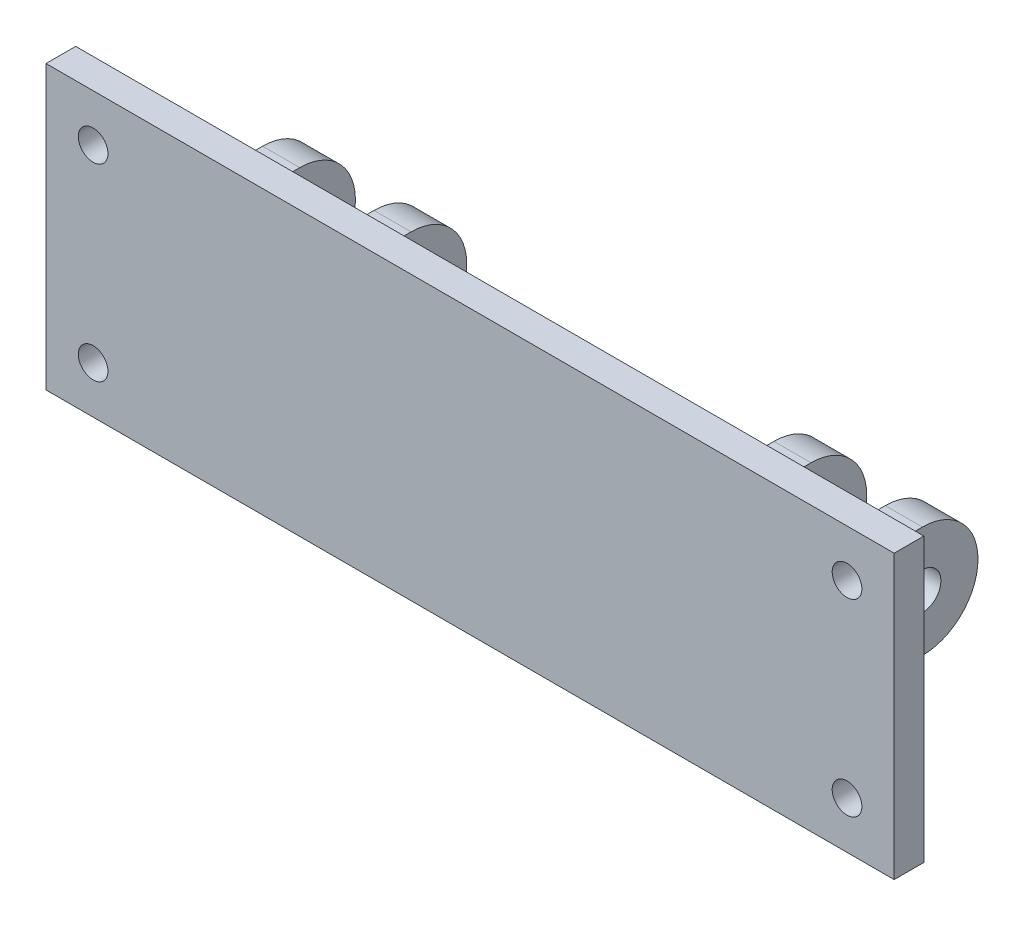
SolidWorks part; units mm, degrees
ref_plane "Front Plane" through (0, 0, 0) normal (0, 0, 1) x (1, 0, 0)
ref_plane "Top Plane" through (0, 0, 0) normal (0, 1, 0) x (1, 0, 0)
ref_plane "Right Plane" through (0, 0, 0) normal (1, 0, 0) x (0, 0, -1)
sketch "Sketch1" plane through (0, 0, 0) normal (0, 0, 1) x (1, 0, 0)
  line L0 (-101.6, 25.4) -> (-101.6, 38.1) construction
  line L1 (-114.3, 38.1) -> (114.3, 38.1)
  line L2 (-114.3, 38.1) -> (-114.3, -38.1)
  line L3 (-114.3, -38.1) -> (114.3, -38.1)
  line L4 (114.3, 38.1) -> (114.3, -38.1)
  line L5 (-58.9, 15) -> (-48.9, 15)
  line L6 (-88.9, 15) -> (-78.9, 15)
  line L7 (-101.6, 25.4) -> (-114.3, 25.4) construction
  line L8 (-88.9, 15) -> (-88.9, -15)
  line L9 (-88.9, -15) -> (-78.9, -15)
  line L10 (-78.9, 15) -> (-78.9, -15)
  line L11 (-88.9, 15) -> (-78.9, -15) construction
  line L12 (-88.9, -15) -> (-78.9, 15) construction
  line L13 (-58.9, 15) -> (-58.9, -15)
  line L14 (-58.9, -15) -> (-48.9, -15)
  line L15 (-48.9, 15) -> (-48.9, -15)
  line L16 (-58.9, 15) -> (-48.9, -15) construction
  line L17 (-58.9, -15) -> (-48.9, 15) construction
  line L18 (0, 0) -> (0, -38.1) construction
  line L19 (58.9, -15) -> (48.9, 15) construction
  line L20 (58.9, 15) -> (48.9, -15) construction
  line L21 (88.9, -15) -> (78.9, 15) construction
  line L22 (88.9, 15) -> (78.9, -15) construction
  line L23 (48.9, 15) -> (48.9, -15)
  line L24 (58.9, -15) -> (48.9, -15)
  line L25 (58.9, 15) -> (58.9, -15)
  line L26 (78.9, 15) -> (78.9, -15)
  line L27 (88.9, -15) -> (78.9, -15)
  line L28 (88.9, 15) -> (88.9, -15)
  line L29 (88.9, 15) -> (78.9, 15)
  line L30 (58.9, 15) -> (48.9, 15)
  circle A0 centre (-101.6, 25.4) radius 4
  circle A7 centre (101.6, 25.4) radius 4
  circle A8 centre (101.6, -25.4) radius 4
  circle A9 centre (-101.6, -25.4) radius 4
  point P0 (0, 0)
  point P16 (-83.9, 0)
  point P23 (-53.9, 0)
  point P36 (53.9, 0)
  point P37 (83.9, 0)
  dimension "D4" = 8
  dimension "D8" = 12.7
  dimension "D6" = 8
  dimension "D7" = 12.7
  dimension "D9" = 8
  dimension "D10" = 12.7
  dimension "D11" = 12.7
  dimension "D12" = 8
  dimension "D13" = 12.7
  dimension "D1" = 76.2
  dimension "D2" = 228.6
  dimension "D3" = 12.7
  dimension "D5" = 12.7
  dimension "D14" = 12.7
  dimension "D15" = 30
  dimension "D16" = 10
  dimension "D17" = 38.1
  dimension "D18" = 25.4
  dimension "D20" = 114.3
  dimension "D21" = 38.1
  dimension "D19" = 2
extrude "Boss-Extrude1" add sketch "Sketch1" along normal blind 8 contours L10 L6 L8 L9 | L15 L5 L13 L14 | L4 L1 L2 L3 A9 A8 A7 A0 L30 L25 L24 L23 L29 L28 L27 L26 L6 L10 L9 L8 L5 L15 L14 L13 | L25 L30 L23 L24 | L28 L29 L26 L27 region at (0, 0, 0) region at (-53.9, 0, 0) region at (-83.9, 0, 0) region at (53.9, 0, 0) region at (83.9, 0, 0)
extrude "Boss-Extrude2" add sketch "Sketch1<3>" against normal blind 40 contours L10 L6 L8 L9 | L15 L5 L13 L14 | L28 L29 L26 L27 | L25 L30 L23 L24 region at (-53.9, 0, 0) region at (-83.9, 0, 0) region at (53.9, 0, 0) region at (83.9, 0, 0)
sketch "Sketch1<3>" plane through (0, 0, 0) normal (0, 0, 1) x (1, 0, 0) same geometry as "Sketch1"
fillet "Fillet1" radius 3 12 edges at (-88.9, 0, 0) (-48.9, 0, 0) (88.9, 0, 0) (48.9, 0, 0) (83.9, 15, 0) (53.9, 15, 0) (-53.9, 15, 0) (-83.9, 15, 0) (-83.9, -15, 0) (-53.9, -15, 0) (53.9, -15, 0) (83.9, -15, 0)
sketch "Sketch2" plane through (-88.9, 0, 0) normal (-1, 0, 0) x (0, 0, 1)
  line L0 (0, 38.1) -> (0, -38.1) construction
  line L1 (0, 38.1) -> (0, -38.1)
  line L4 (-40, -15) -> (-3, -15)
  line L5 (-3, -15) -> (-3, 15)
  line L6 (-3, 15) -> (-40, 15)
  line L7 (-40, 15) -> (-40, -15)
  line L8 (-40, -15) -> (-3, -15)
  line L9 (-3, -15) -> (-3, 15)
  line L10 (-3, 15) -> (-40, 15)
  line L11 (-40, 15) -> (-40, -15)
  circle A0 centre (-25, 0) radius 5
  dimension "D2" = 15
  dimension "D3" = 10
  dimension "D1" = 0
extrude "Cut-Extrude1" cut sketch "Sketch2" against normal through all contours A0 region at (-88.9, 0, -25)
fillet "Fillet2" radius 15 8 edges at (53.9, 15, -40) (53.9, -15, -40) (83.9, 15, -40) (83.9, -15, -40) (-53.9, 15, -40) (-53.9, -15, -40) (-83.9, -15, -40) (-83.9, 15, -40)
